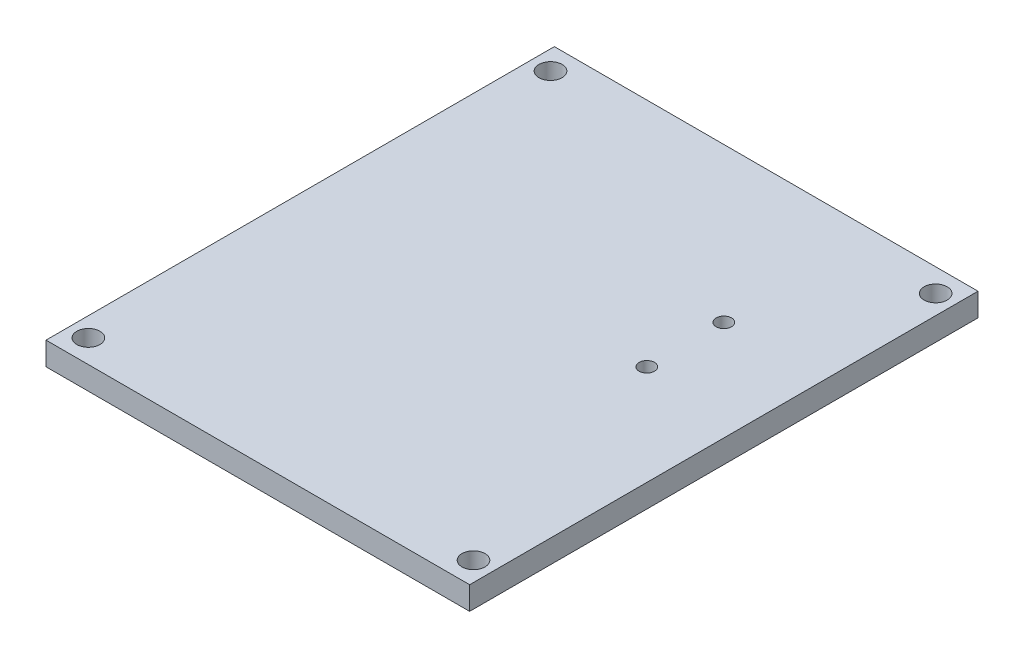
SolidWorks part; units mm, degrees
ref_plane "Plan de face" through (0, 0, 0) normal (0, 0, 1) x (1, 0, 0)
ref_plane "Plan de dessus" through (0, 0, 0) normal (0, 1, 0) x (1, 0, 0)
ref_plane "Plan de droite" through (0, 0, 0) normal (1, 0, 0) x (0, 0, -1)
sketch "Esquisse1" plane through (0, 0, 0) normal (0, 1, 0) x (1, 0, 0)
  line L0 (-27.5396, -33.0827) -> (27.4604, -33.0827)
  line L1 (-27.5396, -33.0827) -> (-27.5396, 32.9173)
  line L2 (-27.5396, 32.9173) -> (27.4604, 32.9173)
  line L3 (27.4604, -33.0827) -> (27.4604, 32.9173)
  line L4 (-27.5396, -33.0827) -> (27.4604, 32.9173) construction
  line L5 (-27.5396, 32.9173) -> (27.4604, -33.0827) construction
  line L6 (-25.0396, -30.0827) -> (24.9604, 29.9173) construction
  line L7 (-25.0396, 29.9173) -> (24.9604, -30.0827) construction
  line L8 (27.4604, 12.9173) -> (14.4604, 12.9173) construction
  line L9 (14.4604, 12.9173) -> (14.4604, 2.9173) construction
  line L10 (27.4604, 32.9173) -> (27.4604, 12.9173) construction
  circle A0 centre (-25.0396, 29.9173) radius 1.5
  circle A1 centre (24.9604, 29.9173) radius 1.5
  circle A2 centre (24.9604, -30.0827) radius 1.5
  circle A3 centre (-25.0396, -30.0827) radius 1.5
  circle A4 centre (14.4604, 12.9173) radius 1
  circle A5 centre (14.4604, 2.9173) radius 1
  point P0 (-0.0396, -0.0827)
  point P5 (-0.0396, -0.0827)
  dimension "D1" = 13
  dimension "D2" = 20
extrude "Boss.-Extru.1" add sketch "Esquisse1" along normal blind 3
